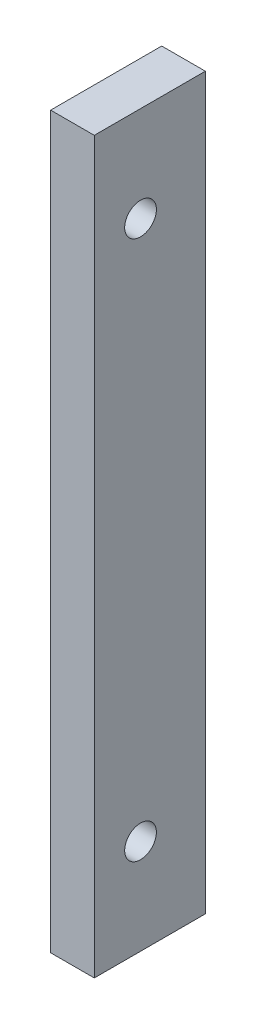
SolidWorks part; units mm, degrees
note: The reader was unsure of these and kept them because the rebuilt part matched: shared geometry of "Sketch2<3>".
material "Pine"
ref_plane "Front Plane" through (0, 0, 0) normal (0, 0, 1) x (1, 0, 0)
ref_plane "Top Plane" through (0, 0, 0) normal (0, 1, 0) x (1, 0, 0)
ref_plane "Right Plane" through (0, 0, 0) normal (1, 0, 0) x (0, 0, -1)
sketch "Sketch1" plane through (0, 0, 0) normal (0, 1, 0) x (1, 0, 0)
  line L1 (0, 0) -> (38.1, 0)
  line L2 (0, 0) -> (0, 88.9)
  line L3 (0, 88.9) -> (38.1, 88.9)
  line L4 (38.1, 0) -> (38.1, 88.9)
  dimension "D1" = 38.1
  dimension "D2" = 88.9
extrude "Boss-Extrude1" add sketch "Sketch1" along normal blind 584.2
sketch "Sketch2" plane through (38.1, 0, 0) normal (1, 0, 0) x (0, 0, -1)
  line L0 (37.0103, 584.2) -> (37.0103, 0) construction
  line L1 (0, 584.2) -> (88.9, 584.2) construction
  line L2 (0, 0) -> (88.9, 0) construction
  line L3 (0, 584.2) -> (0, 0) construction
  circle A0 centre (37.0103, 76.2) radius 12.7
  circle A1 centre (37.0103, 76.2) radius 12.7
  circle A2 centre (37.0103, 508) radius 12.7
  circle A3 centre (37.0103, 508) radius 12.7
  dimension "D1" = 25.4
  dimension "D2" = 25.4
  dimension "D3" = 37.0103
  dimension "D4" = 76.2
  dimension "D5" = 76.2
extrude "Cut-Extrude1" cut sketch "Sketch2" against normal through all contours A3 | A0
extrude "Cut-Extrude2" cut sketch "Sketch2<3>" against normal blind 3.175 contours L0 A2 A3 | A2 L0 A3 | L0 A1 A0 | A1 L0 A0
sketch "Sketch2<3>" plane through (38.1, 0, 0) normal (1, 0, 0) x (0, 0, -1) same geometry as "Sketch2"
